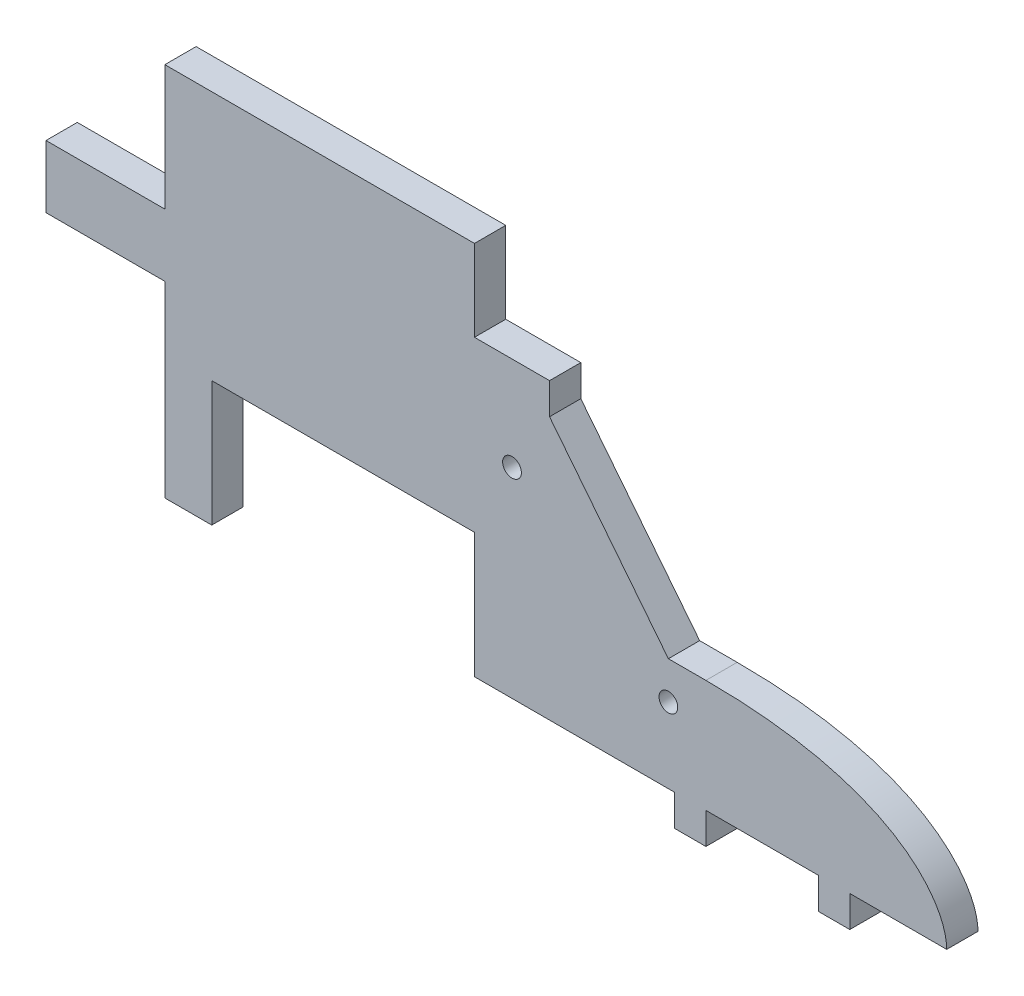
SolidWorks part; units mm, degrees
ref_plane "Plan de face" through (0, 0, 0) normal (0, 0, 1) x (1, 0, 0)
ref_plane "Plan de dessus" through (0, 0, 0) normal (0, 1, 0) x (1, 0, 0)
ref_plane "Plan de droite" through (0, 0, 0) normal (1, 0, 0) x (0, 0, -1)
sketch "Esquisse1" plane through (0, 0, 0) normal (0, 0, 1) x (1, 0, 0)
  line L0 (12, 42) -> (31, 18)
  line L1 (0, 0) -> (32, 0)
  line L2 (0, 0) -> (0, 47)
  line L3 (0, 47) -> (12, 47)
  line L4 (37, 0) -> (37, 18)
  line L6 (12, 47) -> (12, 42)
  line L7 (31, 18) -> (37, 18)
  line L8 (37, 0) -> (37, -5)
  line L9 (37, -5) -> (32, -5)
  line L10 (32, 0) -> (32, -5)
  circle A0 centre (6, 32) radius 1.5
  circle A1 centre (31, 12) radius 1.5
  dimension "D3" = 20
  dimension "D4" = 3
  dimension "D1" = 6
  dimension "D2" = 12
  dimension "D5" = 15
  dimension "D6" = 6
  dimension "D7" = 25
  dimension "D8" = 6
  dimension "D9" = 6
  dimension "D10" = 5
  dimension "D11" = 5
  dimension "D12" = 5
  dimension "D13" = 12
extrude "Boss.-Extru.1" add sketch "Esquisse1" along normal blind 5
sketch "Esquisse2" plane through (0, 0, 0) normal (0, 0, -1) x (-1, 0, 0)
  line L0 (-37, 18) -> (-31, 18) construction
  line L1 (-37, 0) -> (-55, 0)
  line L2 (-37, 0) -> (-37, 18)
  line L3 (-60, 0) -> (-75.5, 0)
  line L4 (42, 0) -> (49.5, 0)
  line L5 (0, 20) -> (0, 60)
  line L6 (0, 60) -> (20, 60)
  line L7 (-10, 167) -> (-1, 167)
  line L8 (0, 0) -> (-32, 0) construction
  line L9 (20, 60) -> (20, 90)
  line L10 (49.5, 120) -> (49.5, 142)
  line L11 (49.5, 0) -> (49.5, 30)
  line L12 (49.5, 30) -> (68.5, 30)
  line L14 (49.5, 40) -> (68.5, 40)
  line L15 (-60, 0) -> (-60, -5)
  line L16 (-60, -5) -> (-55, -5)
  line L17 (-55, 0) -> (-55, -5)
  line L18 (0, 20) -> (42, 20)
  line L19 (68.5, 30) -> (68.5, 40)
  line L20 (49.5, 120) -> (68.5, 120)
  line L21 (49.5, 40) -> (49.5, 110)
  line L22 (0, 47) -> (0, 0) construction
  line L23 (-20, 167) -> (-20, 172)
  line L24 (-20, 172) -> (-10, 172)
  line L25 (-10, 167) -> (-10, 172)
  line L26 (0, 0) -> (-32, 0) construction
  line L27 (42, 20) -> (42, 0)
  line L28 (49.5, 110) -> (68.5, 110)
  line L29 (-37, -5) -> (-37, 18) construction
  line L30 (-1, 167) -> (-1, 142)
  line L31 (20, 90) -> (-25, 90)
  line L32 (-1, 142) -> (49.5, 142)
  line L33 (-20, 167) -> (-25, 167)
  line L34 (-25, 90) -> (-25, 167)
  line L35 (68.5, 120) -> (68.5, 110)
  spline S0 degree 3 poles (-75.5, 0) (-75.5, 5.9822) (-67.6854, 18) (-37, 18) knots 0 0 0 0 1 1 1 1
  dimension "D1" = 38.5
  dimension "D2" = 20
  dimension "D3" = 167
  dimension "D4" = 49.5
  dimension "D5" = 5
  dimension "D6" = 30
  dimension "D7" = 10
  dimension "D8" = 10
  dimension "D9" = 30
  dimension "D10" = 70
  dimension "D11" = 19
  dimension "D12" = 5
  dimension "D13" = 42
  dimension "D14" = 20
  dimension "D15" = 40
  dimension "D16" = 45
  dimension "D17" = 5
  dimension "D19" = 25
  dimension "D21" = 24
extrude "Boss.-Extru.2" add sketch "Esquisse2" against normal blind 5
sketch "Esquisse3" plane through (0, 0, 0) normal (0, 0, -1) x (-1, 0, 0)
  line L0 (20, 60) -> (0, 60) construction
  line L1 (-49.1545, 182.2243) -> (187.1338, 182.2243)
  line L2 (-49.1545, 182.2243) -> (-49.1545, 60)
  line L3 (-49.1545, 60) -> (187.1338, 60)
  line L4 (187.1338, 182.2243) -> (187.1338, 60)
extrude "Enlèv. mat.-Extru.1" cut sketch "Esquisse3" against normal blind 5
